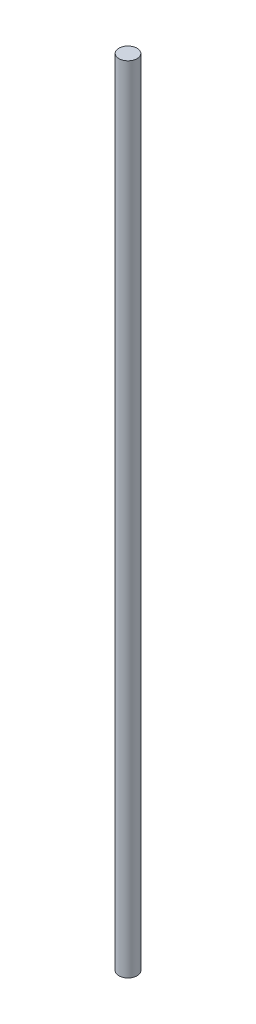
SolidWorks part; units mm, degrees
material "AISI 316 Annealed Stainless Steel Bar (SS)"
ref_plane "Front Plane" through (0, 0, 0) normal (0, 0, 1) x (1, 0, 0)
ref_plane "Top Plane" through (0, 0, 0) normal (0, 1, 0) x (1, 0, 0)
ref_plane "Right Plane" through (0, 0, 0) normal (1, 0, 0) x (0, 0, -1)
sketch "Sketch1" plane through (0, 0, 0) normal (0, 1, 0) x (1, 0, 0)
  circle A0 centre (0, 0) radius 4
  dimension "D1" = 8
extrude "Boss-Extrude1" add sketch "Sketch1" against normal blind 350
equation "\"rod_diameter\"= 8"
equation "\"rod_hole_thickness\"= 4"
equation "\"rod_radius\"= \"rod_diameter\" / 2"
equation "\"platter_diameter\"= 320"
equation "\"platter_radius\"= \"platter_diameter\" / 2"
equation "\"extruder_mount_hole_spacing\"= 75"
equation "\"arm_rod_spacing\"= 40"
equation "\"motor_level_rod_spacing\"= 15"
equation "\"linear_bearing_diameter\"= 15"
equation "\"z_rod_spacing\"= 75"
equation "\"platter_rod_spacing\"= 50"
equation "\"rod_nut_thickness\"= 6.5"
equation "\"rod_nut_inscribed_diameter\"= 13"
equation "\"z_height\"= 350"
equation "\"D1@Sketch1\"= \"rod_diameter\""
equation "\"D1@Boss-Extrude1\"= \"z_height\""
